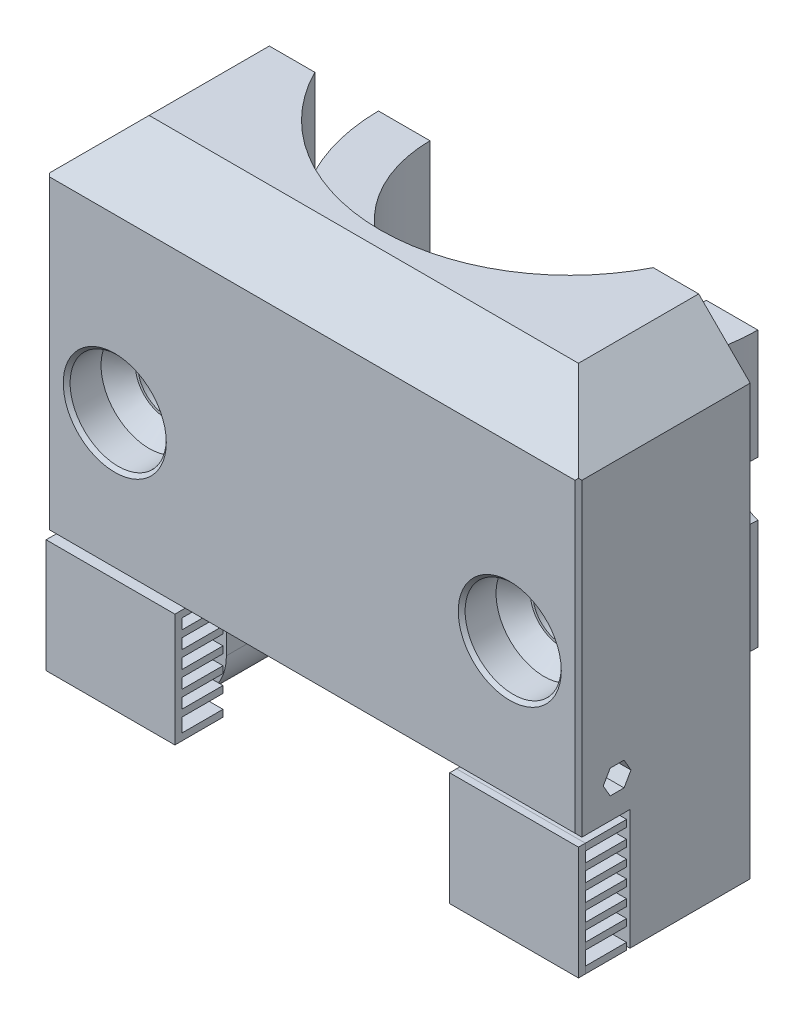
SolidWorks part; units mm, degrees
ref_plane "Front Plane" through (0, 0, 0) normal (0, 0, 1) x (1, 0, 0)
ref_plane "Top Plane" through (0, 0, 0) normal (0, 1, 0) x (1, 0, 0)
ref_plane "Right Plane" through (0, 0, 0) normal (1, 0, 0) x (0, 0, -1)
sketch "Sketch1" plane through (0, 0, 0) normal (0, 1, 0) x (1, 0, 0)
  circle A0 centre (0, 0) radius 8.05
  circle A1 centre (0, 0) radius 11.05
  dimension "D1" = 16.1
  dimension "D2" = 3
extrude "Boss-Extrude1" add sketch "Sketch1" along normal blind 7.1
sketch "Sketch2" plane through (0, 0, 0) normal (0, -1, 0) x (-1, 0, 0)
  circle A0 centre (0, 0) radius 6.05
  circle A1 centre (0, 0) radius 11.05
  dimension "D1" = 12.1
  dimension "D2" = 5
extrude "Boss-Extrude2" add sketch "Sketch2" along normal blind 5.9
sketch "Sketch3" plane through (0, -5.9, 0) normal (0, -1, 0) x (-1, 0, 0)
  circle A0 centre (0, 0) radius 8.05
  circle A1 centre (0, 0) radius 11.05
  dimension "D1" = 16.1
  dimension "D2" = 3
extrude "Boss-Extrude3" add sketch "Sketch3" along normal blind 3
sketch "Sketch5" plane through (0, 7.1, 0) normal (0, 1, 0) x (1, 0, 0)
  line L0 (9.8541, 5) -> (27, 5)
  line L1 (-27, -5) -> (-9.8541, -5)
  line L2 (-27, -5) -> (-27, 5)
  line L3 (-27, 5) -> (-9.8541, 5)
  line L4 (27, -5) -> (27, 5)
  line L5 (9.8541, -5) -> (27, -5)
  circle A0 centre (0, 0) radius 11.05 construction
  circle A1 centre (-21.75, 0) radius 1.5
  circle A2 centre (21.75, 0) radius 1.5
  circle A3 centre (0, 0) radius 2.05
  circle A4 centre (0, 0) radius 11.05
  circle M6 centre (0, 0) radius 11.05
  circle M7 centre (0, 0) radius 8.05
  dimension "D5" = 3
  dimension "D8" = 4.1
  dimension "D11" = 22.1
  dimension "D1" = 10
  dimension "D2" = 54
  dimension "D3" = 27
  dimension "D4" = 5
  dimension "D6" = 5.25
  dimension "D9" = 5
  dimension "D10" = 27
  dimension "D7" = 2
extrude "Boss-Extrude5" add sketch "Sketch5" along normal blind 5 contours L3 L2 L1 A1 M6 | M6 M7 | L5 L4 L0 A2 M6 | A3 M7 region at (18.6942, 7.1, 0) region at (10.4429, 7.1, -2.4978) region at (-18.6942, 7.1, 0) region at (-7.8223, 7.1, 0)
sketch "Sketch6" plane through (0, 12.1, 0) normal (0, 1, 0) x (1, 0, 0)
  line L0 (-27, -5) -> (-9.8541, -5) construction
  line L1 (-15.5, -5) -> (-9.8541, -5)
  line L2 (-15.5, -5) -> (-15.5, -15)
  line L3 (-15.5, -15) -> (15.5, -15)
  line L4 (15.5, -5) -> (15.5, -15)
  line L5 (9.8541, -5) -> (15.5, -5)
  circle A0 centre (0, 0) radius 2.05 construction
  arc A1 (-9.8541, -5) -> (9.8541, -5) centre (0, 0) ccw
  point P6 (0, -15)
  dimension "D4" = 11.05
  dimension "D1" = 31
  dimension "D3" = 10
extrude "Boss-Extrude6" add sketch "Sketch6" against normal blind 28
sketch "Sketch7" plane through (0, 0, 15) normal (0, 0, 1) x (1, 0, 0)
  line L0 (-15.5, -15.9) -> (15.5, -15.9) construction
  line L1 (-15.5, -15.9) -> (-15.5, 12.1) construction
  circle A0 centre (-12, -12.4) radius 1.45
  circle A1 centre (12, -12.4) radius 1.45
  dimension "D4" = 2.9
  dimension "D1" = 3.5
  dimension "D2" = 3.5
  dimension "D3" = 2
extrude "Cut-Extrude1" cut sketch "Sketch7" against normal blind 10
sketch "Sketch20" plane through (0, 0, 15) normal (0, 0, 1) x (1, 0, 0)
  circle A0 centre (-12, -12.4) radius 2.15
  circle A1 centre (12, -12.4) radius 2.15
  dimension "D1" = 4.3
  dimension "D2" = 4.3
extrude "Cut-Extrude13" cut sketch "Sketch20" against normal blind 7.2
sketch "Sketch8" plane through (0, -15.9, 0) normal (0, -1, 0) x (-1, 0, 0)
  line L0 (15.5, -15) -> (-15.5, -15) construction
  line L1 (-8, -15) -> (8, -15)
  line L2 (-8, -15) -> (-8, -5)
  line L3 (-8, -5) -> (8, -5)
  line L4 (8, -15) -> (8, -5)
  circle A0 centre (0, 0) radius 12
  point P6 (0, -15)
  line M6 (15.5, -5) -> (9.8541, -5)
  arc M7 (9.8541, -5) -> (-9.8541, -5) centre (0, 0) cw
  line M8 (-9.8541, -5) -> (-15.5, -5)
  line M10 (-15.5, -15) -> (15.5, -15)
  dimension "D4" = 24
  dimension "D1" = 10
  dimension "D2" = 16
  dimension "D3" = 0
extrude "Cut-Extrude2" cut sketch "Sketch8" against normal blind 7 contours A0 L2 L4 M10 | L2 A0 L4 M7 | L4 L3 L2 M7 | A0 L2 M8 M7 | L4 A0 M6 M7 region at (0, -15.9, 12.9198) region at (9.3108, -15.9, 6.7422) region at (7.8341, -15.9, 8.2834) region at (-9.3108, -15.9, 6.7422) region at (0, -15.9, 7.5931)
ref_plane "Plane1" through (0, 0, 0.1) normal (0, 0, 1) x (1, 0, 0)
sketch "Sketch11" plane through (0, 0, 0.1) normal (0, 0, 1) x (1, 0, 0)
  line L0 (9.8541, 7.1) -> (27, 7.1) construction
  line L1 (33.7519, -27.3661) -> (-35.342, -27.3661)
  line L2 (33.7519, -27.3661) -> (33.7519, 7.1)
  line L3 (33.7519, 7.1) -> (-35.342, 7.1)
  line L4 (-35.342, -27.3661) -> (-35.342, 7.1)
  dimension "D1" = 0
extrude "Cut-Extrude4" cut sketch "Sketch11" against normal through all
sketch "Sketch13" plane through (0, 12.1, 0) normal (0, 1, 0) x (1, 0, 0)
  line L0 (27, -5) -> (27, 5) construction
  line L1 (-27, 5) -> (27, 5)
  line L2 (-27, 5) -> (-27, -5)
  line L3 (-27, -5) -> (27, -5)
  line L4 (27, 5) -> (27, -5)
  line L5 (15.5, -5) -> (27, -5) construction
  circle A0 centre (0, 0) radius 11.05
  line M1 (-27, -5) -> (-15.5, -5)
  line M5 (15.5, -5) -> (27, -5)
  line M6 (27, -5) -> (27, 5)
  line M7 (27, 5) -> (9.8541, 5)
  arc M8 (9.8541, 5) -> (-9.8541, 5) centre (0, 0) ccw
  line M9 (-9.8541, 5) -> (-27, 5)
  line M10 (-27, 5) -> (-27, -5)
  circle M11 centre (-21.75, 0) radius 1.5
  circle M12 centre (21.75, 0) radius 1.5
  circle M13 centre (0, 0) radius 2.05
  dimension "D1" = 22.1
extrude "Cut-Extrude6" cut sketch "Sketch13" against normal blind 5 contours A0 L3 M9 M10 M1 M11 | A0 L3 M5 M6 M7 M12 | L3 A0 | L3 A0 L1 M13 | L1 M8 region at (-18.6942, 12.1, 0) region at (0, 12.1, -7.4876) region at (0, 12.1, -4.7574) region at (18.6942, 12.1, 0) region at (0, 12.1, 7.4876)
sketch "Sketch14" plane through (0, 0, 15) normal (0, 0, 1) x (1, 0, 0)
  line L0 (15.5, -15.9) -> (15.5, 12.1) construction
  line L1 (-15.5, -15.9) -> (-15.5, 12.1) construction
  line L2 (-15.5, 12.1) -> (15.5, 12.1) construction
  circle A0 centre (11.5, -0.9) radius 1.65
  circle A1 centre (-11.5, -0.9) radius 1.65
  dimension "D1" = 3.3
  dimension "D2" = 3.3
  dimension "D3" = 4
  dimension "D4" = 4
  dimension "D5" = 13
  dimension "D6" = 13
extrude "Cut-Extrude7" cut sketch "Sketch14" against normal through all
sketch "Sketch15" plane through (0, 0, 15) normal (0, 0, 1) x (1, 0, 0)
  circle A0 centre (11.5, -0.9) radius 2.8
  circle A1 centre (-11.5, -0.9) radius 2.8
  dimension "D1" = 5.6
  dimension "D2" = 5.6
extrude "Cut-Extrude8" cut sketch "Sketch15" against normal blind 3
sketch "Sketch21" plane through (0, 0, 15) normal (0, 0, 1) x (1, 0, 0)
  line L0 (-15.5, -15.9) -> (-15.5, 12.1) construction
  line L1 (15.5, -15.9) -> (-15.5, -15.9)
  line L2 (15.5, -15.9) -> (15.5, -8.9)
  line L3 (15.5, -8.9) -> (-15.5, -8.9)
  line L4 (-15.5, -15.9) -> (-15.5, -8.9)
  line L5 (8, -8.9) -> (-8, -8.9) construction
  dimension "D1" = 0
extrude "Cut-Extrude14" cut sketch "Sketch21" against normal blind 3
chamfer "倒角2" distance 3 angle 45 3 edges at (0, 12.1, 15) (15.5, 12.1, 10) (-15.5, 12.1, 10)
fillet "Fillet2" radius 3 2 edges at (8, -15.9, 10.4721) (-8, -15.9, 10.4721)
chamfer "倒角1" distance 1 angle 45 2 edges at (14.3, -0.9, 12) (-8.7, -0.9, 12)
sketch "草图1" plane through (0, 0, 15) normal (0, 0, 1) x (1, 0, 0)
  line L1 (-15.5, -9.3) -> (-8, -9.3)
  line L2 (-15.5, -9.3) -> (-15.5, -15.9)
  line L3 (-15.5, -15.9) -> (-8, -15.9)
  line L4 (-8, -9.3) -> (-8, -15.9)
  line L12 (0, 9.1) -> (0, -4.6632) construction
  line L13 (-15.5, -8.9) -> (-15.5, -15.9) construction
  line L14 (15.5, -15.9) -> (8, -15.9)
  line L15 (8, -9.3) -> (8, -15.9)
  line L16 (15.5, -9.3) -> (8, -9.3)
  line L17 (15.5, -9.3) -> (15.5, -15.9)
  line L19 (-8, -12.9) -> (-8, -8.9) construction
  line L20 (-15.5, -15.9) -> (-11, -15.9) construction
  dimension "D1" = 0
  dimension "D2" = 0
  dimension "D3" = 0
extrude "凸台-拉伸1" add sketch "草图1" against normal blind 0.4
sketch "草图2" plane through (0, 0, 14.6) normal (0, 0, -1) x (-1, 0, 0)
  line L0 (15.5, -9.3) -> (15.5, -15.9) construction
  line L1 (8, -9.3) -> (15.5, -9.3)
  line L2 (8, -9.3) -> (8, -9.7)
  line L3 (8, -9.7) -> (15.5, -9.7)
  line L4 (15.5, -9.3) -> (15.5, -9.7)
  line L5 (8, -10.3) -> (8, -10.7)
  line L6 (8, -10.3) -> (15.5, -10.3)
  line L7 (15.5, -10.3) -> (15.5, -10.7)
  line L8 (8, -10.7) -> (15.5, -10.7)
  line L9 (8, -11.3) -> (8, -11.7)
  line L10 (8, -11.3) -> (15.5, -11.3)
  line L11 (15.5, -11.3) -> (15.5, -11.7)
  line L12 (8, -11.7) -> (15.5, -11.7)
  line L13 (8, -12.3) -> (8, -12.7)
  line L14 (8, -12.3) -> (15.5, -12.3)
  line L15 (15.5, -12.3) -> (15.5, -12.7)
  line L16 (8, -12.7) -> (15.5, -12.7)
  line L17 (8, -13.3) -> (8, -13.7)
  line L18 (8, -13.3) -> (15.5, -13.3)
  line L19 (15.5, -13.3) -> (15.5, -13.7)
  line L20 (8, -13.7) -> (15.5, -13.7)
  line L21 (8, -14.3) -> (8, -14.7)
  line L22 (8, -14.3) -> (15.5, -14.3)
  line L23 (15.5, -14.3) -> (15.5, -14.7)
  line L24 (8, -14.7) -> (15.5, -14.7)
  line L25 (0, 0) -> (0, -13.3) construction
  line L26 (-8, -9.7) -> (-15.5, -9.7)
  line L27 (-15.5, -9.3) -> (-15.5, -9.7)
  line L28 (-8, -9.3) -> (-15.5, -9.3)
  line L29 (-8, -9.3) -> (-8, -9.7)
  line L30 (-8, -10.3) -> (-15.5, -10.3)
  line L31 (-15.5, -10.3) -> (-15.5, -10.7)
  line L32 (-8, -10.7) -> (-15.5, -10.7)
  line L33 (-8, -10.3) -> (-8, -10.7)
  line L34 (-8, -11.3) -> (-15.5, -11.3)
  line L35 (-15.5, -11.3) -> (-15.5, -11.7)
  line L36 (-8, -11.7) -> (-15.5, -11.7)
  line L37 (-8, -11.3) -> (-8, -11.7)
  line L38 (-8, -12.3) -> (-15.5, -12.3)
  line L39 (-15.5, -12.3) -> (-15.5, -12.7)
  line L40 (-8, -12.7) -> (-15.5, -12.7)
  line L41 (-8, -12.3) -> (-8, -12.7)
  line L42 (-8, -13.3) -> (-15.5, -13.3)
  line L43 (-15.5, -13.3) -> (-15.5, -13.7)
  line L44 (-8, -13.7) -> (-15.5, -13.7)
  line L45 (-8, -13.3) -> (-8, -13.7)
  line L46 (-8, -14.3) -> (-15.5, -14.3)
  line L47 (-15.5, -14.3) -> (-15.5, -14.7)
  line L48 (-8, -14.7) -> (-15.5, -14.7)
  line L49 (-8, -14.3) -> (-8, -14.7)
  line L50 (-15.5, -15.9) -> (-15.5, 9.1) construction
  line L51 (-8, -15.9) -> (-15.5, -15.9)
  line L52 (-8, -15.9) -> (-8, -15.5)
  line L53 (-8, -15.5) -> (-15.5, -15.5)
  line L54 (-15.5, -15.9) -> (-15.5, -15.5)
  line L55 (15.5, -15.9) -> (15.5, 9.1) construction
  line L56 (8, -15.9) -> (15.5, -15.9)
  line L57 (8, -15.9) -> (8, -15.5)
  line L58 (8, -15.5) -> (15.5, -15.5)
  line L59 (15.5, -15.9) -> (15.5, -15.5)
  dimension "D1" = 0.4
  dimension "D3" = 0.4
  dimension "D4" = 0.4
  dimension "D2" = 6
extrude "凸台-拉伸2" add sketch "草图2" along normal offset from surface (2.4 mm away) 0.2 up to face at (11.4757, -12.6243, 12)
sketch "草图5" plane through (15.5, 0, 0) normal (1, 0, 0) x (0, 0, -1)
  line L1 (-11.9417, -6.94) -> (-12.3459, -6.24)
  line L2 (-12.3459, -6.24) -> (-13.1541, -6.24)
  line L3 (-13.1541, -6.24) -> (-13.5583, -6.94)
  line L4 (-13.5583, -6.94) -> (-13.1541, -7.64)
  line L5 (-13.1541, -7.64) -> (-12.3459, -7.64)
  line L6 (-12.3459, -7.64) -> (-11.9417, -6.94)
  line L7 (-15, -8.9) -> (-15, 9.1) construction
  line L8 (-12, -8.9) -> (-15, -8.9) construction
  circle A0 centre (-12.75, -6.94) radius 0.7 construction
  dimension "D3" = 1.4
  dimension "D1" = 1.96
  dimension "D2" = 2.25
ref_plane "基准面1" through (0, 0, 0) normal (1, 0, 0) x (0, 0, -1)
extrude "切除-拉伸1" cut sketch "草图5" against normal blind 5
mirror "镜向1" about plane through (0, 0, 0) normal (1, 0, 0) of "切除-拉伸1"
chamfer "倒角4" distance 0.2 angle 45 5 edges at (15.5, 0.1, 15) (0, -8.9, 15) (-15.5, 0.1, 15) (14.3, -0.9, 15) (-8.7, -0.9, 15)
equation "\"D3@Sketch5\"=\"D2@Sketch5\"/2"
equation "\"D4@Sketch5\"=\"D1@Sketch5\"/2"
equation "\"D6@Sketch5\"=\"D2@Sketch5\"/2-43.5/2"
equation "\"D9@Sketch5\"=\"D4@Sketch5\""
equation "\"D10@Sketch5\"=\"D3@Sketch5\""
equation "\"D1@Sketch6\"=30+1"
